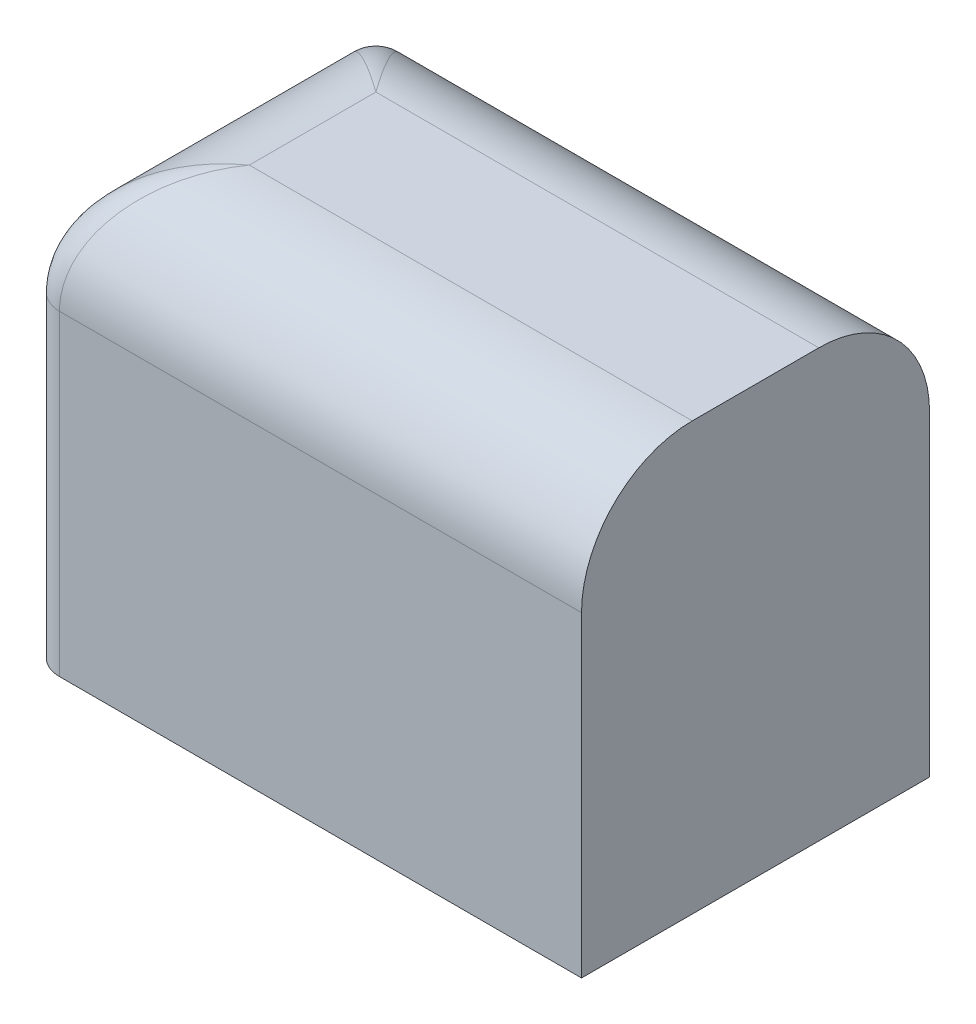
SolidWorks part; units mm, degrees
material "2024 Alloy"
ref_plane "Front" through (0, 0, 0) normal (0, 0, 1) x (1, 0, 0)
ref_plane "Top" through (0, 0, 0) normal (0, 1, 0) x (1, 0, 0)
ref_plane "Right" through (0, 0, 0) normal (1, 0, 0) x (0, 0, -1)
sketch "Sketch1" plane through (0, 0, 0) normal (0, 1, 0) x (1, 0, 0)
  line L0 (-13, 11) -> (-13, -11)
  line L1 (-13, -11) -> (22, -11)
  line L2 (22, -11) -> (22, 11)
  line L3 (22, 11) -> (-13, 11)
  line L4 (0, 0) -> (0, 8.9776) construction
  line L5 (0, 0) -> (-13, 0) construction
  dimension "D1" = 22
  dimension "D2" = 13
  dimension "D3" = 35
extrude "Boss-Extrude1" add sketch "Sketch1" along normal blind 27
sketch "Sketch2" plane through (-13, 0, 0) normal (-1, 0, 0) x (0, 0, 1)
  line L0 (0, 27) -> (0, 3) construction
  line L1 (-11, 27) -> (11, 27) construction
  circle A0 centre (0, 15) radius 9.652
  dimension "D2" = 19.304
  dimension "D1" = 24
extrude "Cut-Extrude1" cut sketch "Sketch2" against normal offset from surface (32.5 mm away) 2.5 up to face at (22, 13.5, 0)
hole_wizard "M6x1.0 Tapped Hole1" positions "Sketch4" profile "Sketch3" tap size "M6x1.0" standard "BSI"
sketch "Sketch4" plane through (0, 0, 0) normal (0, 1, 0) x (1, 0, 0)
  point P0 (0, 0)
sketch "Sketch3" plane through (0, 0, 0) normal (1, 0, 0) x (0, 0, -1)
  line L0 (0, 0) -> (0, 7.5022)
  line L1 (0, 7.5022) -> (2.5, 6)
  line L2 (2.5, 6) -> (2.5, 0)
  line L5 (2.5, 0) -> (0, 0)
  line L10 (0, 7.5022) -> (-2.5, 6) construction
  line L11 (0, -6.35) -> (0, 107.95) construction
  dimension "Tap Drill Dia." = 5
  dimension "Tap Drill Depth" = 6
  dimension "Drill Angle" = 118
cosmetic thread "Hole Thread1" parameters "D1"=1.6774, "D2"=6
fillet "Fillet2" radius 2 2 edges at (-13, 13.5, 11) (-13, 13.5, -11)
fillet "Fillet1" radius 7 5 edges at (5.5, 27, -11) (5.5, 27, 11) (-12.4142, 27, -10.4142) (-13, 27, 0) (-12.4142, 27, 10.4142)
sketch "Sketch5" plane through (0, 0, 0) normal (0, -1, 0) x (1, 0, 0)
  line L0 (22, 11) -> (22, -11) construction
  line L1 (-11, 9) -> (20, 9)
  line L2 (-11, 9) -> (-11, -9)
  line L3 (-11, -9) -> (20, -9)
  line L4 (20, 9) -> (20, -9)
  arc A0 (-13, -9) -> (-11, -11) centre (-11, -9) ccw construction
  circle A1 centre (0, 0) radius 5
  dimension "D2" = 10
  dimension "D1" = 2
extrude "Cut-Extrude2" cut sketch "Sketch5" against normal blind 4
fillet "Fillet3" radius 2 4 edges at (-11, 2, -9) (20, 2, -9) (20, 2, 9) (-11, 2, 9)
